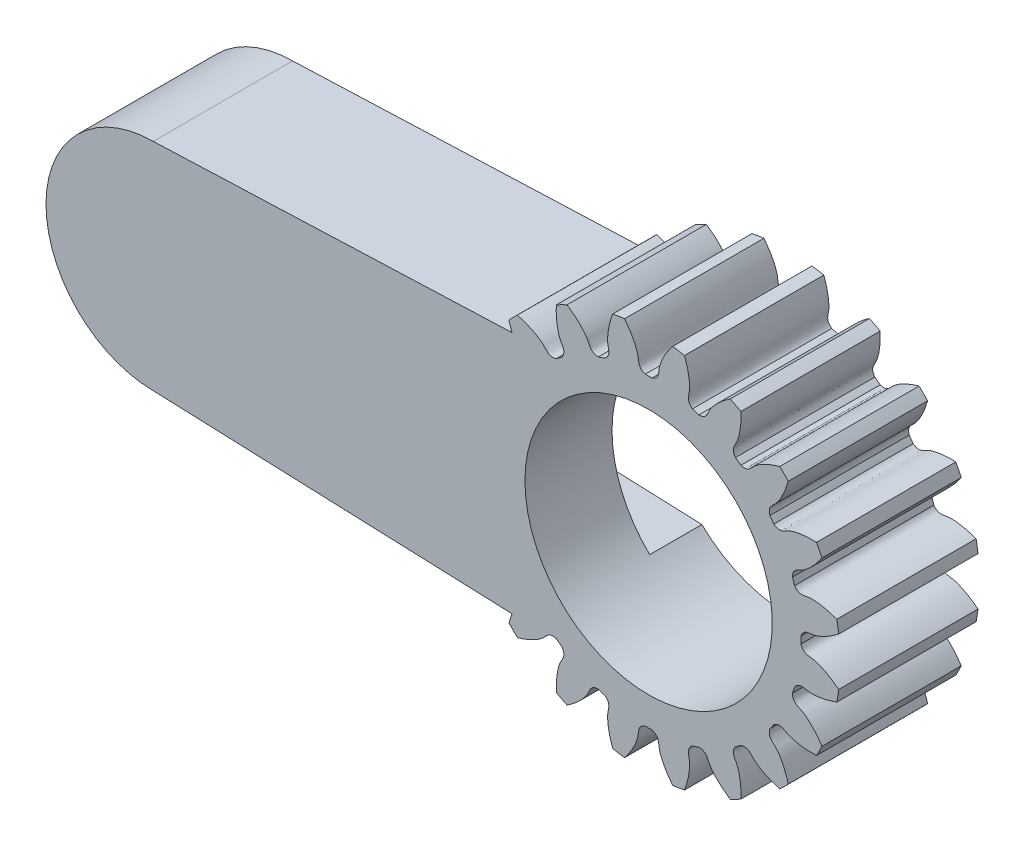
SolidWorks part; units mm, degrees
ref_plane "前视基准面" through (0, 0, 0) normal (0, 0, 1) x (1, 0, 0)
ref_plane "上视基准面" through (0, 0, 0) normal (0, 1, 0) x (1, 0, 0)
ref_plane "右视基准面" through (0, 0, 0) normal (1, 0, 0) x (0, 0, -1)
other "Configuration Table"
sketch "草图1" plane through (0, 0, 0) normal (0, 0, 1) x (1, 0, 0)
  circle A0 centre (0, 0) radius 5.5
extrude "凸台-拉伸1" add sketch "草图1" along normal blind 4
ref_axis "基准轴1" through (0, 0, 4) along (0, 0, -1)
sketch "草图2" plane through (0, 0, 0) normal (0, 0, 1) x (1, 0, 0)
  line L0 (0, 0) -> (0, 5.5) construction
  circle A0 centre (0, 0) radius 5.5 construction
  arc A1 (0.0967, 4.3739) -> (-0.0967, 4.3739) centre (0, 0) ccw
  arc A2 (1.5906, 6.2491) -> (-1.5906, 6.2491) centre (0, 0) ccw
  spline S0 degree 3 poles (0.0967, 4.3739) (0.3056, 4.4467) (0.2785, 4.5936) (0.3064, 4.735) (0.3094, 4.7488) (0.3132, 4.7643) (0.3176, 4.7816) (0.323, 4.8006) (0.3293, 4.8213) (0.3365, 4.8436) (0.3448, 4.8676) (0.3543, 4.8932) (0.3649, 4.9203) (0.3768, 4.9489) (0.3901, 4.979) (0.4047, 5.0106) (0.4208, 5.0435) (0.4383, 5.0778) (0.4575, 5.1134) (0.4783, 5.1502) (0.5008, 5.1882) (0.525, 5.2274) (0.551, 5.2676) (0.5789, 5.3089) (0.6087, 5.3511) (0.6404, 5.3943) (0.6741, 5.4383) (0.7099, 5.4831) (0.7477, 5.5286) (0.7877, 5.5748) (0.8299, 5.6215) (0.8743, 5.6688) (0.9209, 5.7165) (0.9698, 5.7646) (1.0211, 5.813) (1.0747, 5.8617) (1.1306, 5.9104) (1.189, 5.9593) (1.2498, 6.0082) (1.313, 6.057) (1.3788, 6.1056) (1.4707, 6.1708) (1.542, 6.2182) (1.5906, 6.2491) knots 0 0 0 0 0.165916 0.170906 0.176664 0.183189 0.190482 0.198542 0.207371 0.216967 0.22733 0.238462 0.250361 0.263027 0.276462 0.290664 0.305634 0.321371 0.337876 0.355149 0.37319 0.391998 0.411574 0.431917 0.453028 0.474907 0.497554 0.520968 0.54515 0.570099 0.595817 0.622302 0.649554 0.677575 0.706363 0.735918 0.766242 0.797333 0.829191 0.861818 0.895212 0.929373 1 1 1 1
  spline S1 degree 3 poles (-0.0967, 4.3739) (-0.3056, 4.4467) (-0.2785, 4.5936) (-0.3064, 4.735) (-0.3094, 4.7488) (-0.3132, 4.7643) (-0.3176, 4.7816) (-0.323, 4.8006) (-0.3293, 4.8213) (-0.3365, 4.8436) (-0.3448, 4.8676) (-0.3543, 4.8932) (-0.3649, 4.9203) (-0.3768, 4.9489) (-0.3901, 4.979) (-0.4047, 5.0106) (-0.4208, 5.0435) (-0.4383, 5.0778) (-0.4575, 5.1134) (-0.4783, 5.1502) (-0.5008, 5.1882) (-0.525, 5.2274) (-0.551, 5.2676) (-0.5789, 5.3089) (-0.6087, 5.3511) (-0.6404, 5.3943) (-0.6741, 5.4383) (-0.7099, 5.4831) (-0.7477, 5.5286) (-0.7877, 5.5748) (-0.8299, 5.6215) (-0.8743, 5.6688) (-0.9209, 5.7165) (-0.9698, 5.7646) (-1.0211, 5.813) (-1.0747, 5.8617) (-1.1306, 5.9104) (-1.189, 5.9593) (-1.2498, 6.0082) (-1.313, 6.057) (-1.3788, 6.1056) (-1.4707, 6.1708) (-1.542, 6.2182) (-1.5906, 6.2491) knots 0 0 0 0 0.165916 0.170906 0.176664 0.183189 0.190482 0.198542 0.207371 0.216967 0.22733 0.238462 0.250361 0.263027 0.276462 0.290664 0.305634 0.321371 0.337876 0.355149 0.37319 0.391998 0.411574 0.431917 0.453028 0.474907 0.497554 0.520968 0.54515 0.570099 0.595817 0.622302 0.649554 0.677575 0.706363 0.735918 0.766242 0.797333 0.829191 0.861818 0.895212 0.929373 1 1 1 1
extrude "切除-拉伸1" cut sketch "草图2" along normal through all
pattern_circular "阵列(圆周)1" count 20 over 360 about axis through (0, 0, 4) along (0, 0, -1) of "切除-拉伸1"
sketch "草图3" plane through (0, 0, 0) normal (0, 0, 1) x (1, 0, 0)
  circle A0 centre (0, 0) radius 5 construction
  dimension "Dn" = 10
sketch "草图4" plane through (0, 0, 0) normal (0, 0, -1) x (-1, 0, 0)
  circle A0 centre (0, 0) radius 3.55
  dimension "D1" = 7.1
extrude "切除-拉伸2" cut sketch "草图4" against normal through all
sketch "草图5" plane through (0, 0, 0) normal (0, 0, -1) x (-1, 0, 0)
  line L2 (0, 0) -> (18.889, 0) construction
  line L5 (2.4698, -2.55) -> (14.2, -2.1)
  line L6 (2.4698, 2.55) -> (2.4698, -2.55)
  line L7 (2.4698, 2.55) -> (14.2, 2.1)
  line L8 (14.2, -2.1) -> (14.2, 2.1) construction
  arc A2 (14.2, 2.1) -> (14.2, -2.1) centre (14.2, 0) cw
  circle A3 centre (0, 0) radius 3.55 construction
  dimension "D1" = 2.1
  dimension "D2" = 14.2
  dimension "D3" = 5.1
extrude "拉伸-薄壁4" add sketch "草图5" against normal blind 1.5 thin thin type one direction wall 1
sketch "草图6" plane through (0, 0, 0) normal (0, 0, -1) x (-1, 0, 0)
  line L0 (2.4698, 2.55) -> (5.9359, 2.417)
  line L1 (14.2, 2.1) -> (4.9212, 2.456) construction
  line L2 (2.4698, -2.55) -> (5.9359, -2.417)
  line L3 (2.4698, 2.55) -> (2.4698, -2.55) construction
  line L4 (4.9212, -2.456) -> (14.2, -2.1) construction
  line L5 (5.9359, -2.417) -> (5.9359, 2.417)
  line L6 (1.4698, -3.2314) -> (1.4698, 3.2314)
  arc A0 (1.4698, -3.2314) -> (2.4698, -2.55) centre (0, 0) ccw
  arc A1 (2.4698, -2.55) -> (2.4698, 2.55) centre (0, 0) ccw construction
  arc A2 (2.4698, 2.55) -> (1.4698, 3.2314) centre (0, 0) ccw
extrude "切除-拉伸3" cut sketch "草图6" against normal blind 1.5
sketch "草图7" plane through (0, 0, 0) normal (0, 0, -1) x (-1, 0, 0)
  line L0 (3.9194, -3.4951) -> (14.221, -3.0999) construction
  line L1 (14.221, 3.0999) -> (3.9194, 3.4951) construction
  line L2 (3.9194, -3.4951) -> (14.221, -3.0999)
  line L3 (14.221, 3.0999) -> (3.9194, 3.4951)
  line L4 (3.9194, 3.4951) -> (2.4698, 2.55)
  line L5 (3.9194, -3.4951) -> (2.4698, -2.55)
  arc A0 (2.4698, -2.55) -> (2.4698, 2.55) centre (0, 0) ccw
  arc A1 (14.221, -3.0999) -> (14.221, 3.0999) centre (14.2, 0) ccw construction
  arc A2 (14.221, -3.0999) -> (14.221, 3.0999) centre (14.2, 0) ccw
  arc A3 (2.4698, 2.55) -> (2.4698, -2.55) centre (0, 0) ccw construction
extrude "凸台-拉伸3" add sketch "草图7" against normal up to surface (4 mm away) from surface up to face at (-3.55, 0, 4) starting at face at (-6.9589, -0.0431, 1.5)
